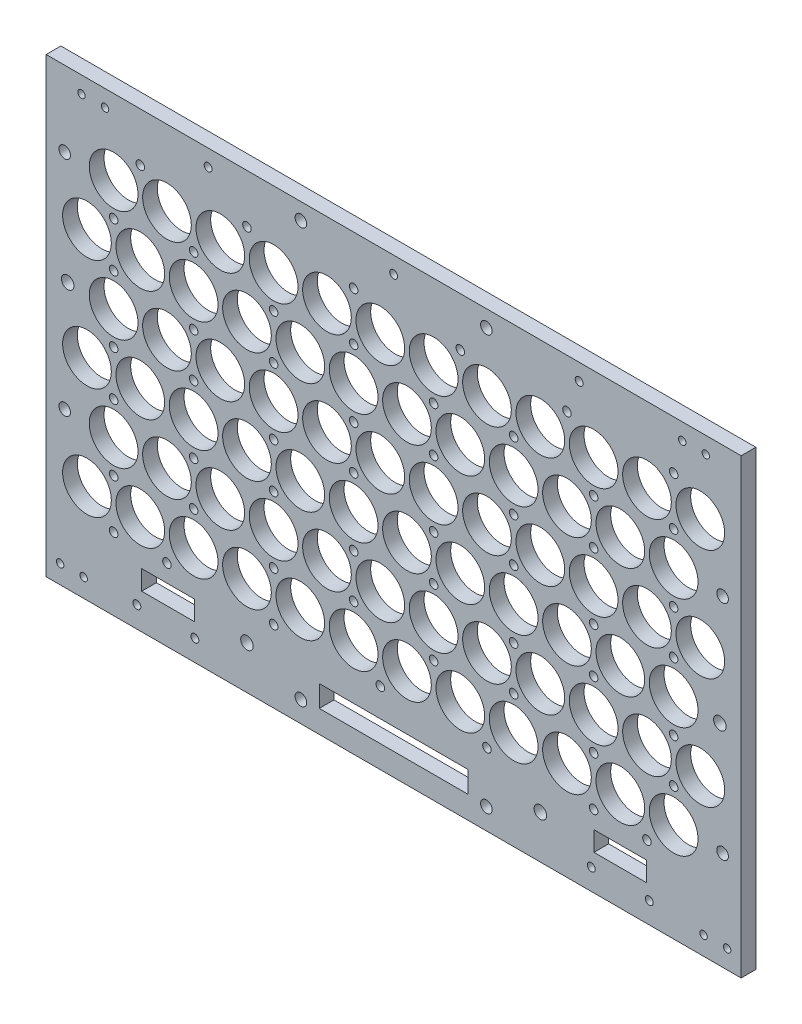
SolidWorks part; units mm, degrees
material "ABS"
ref_plane "X-Y Datum" through (0, 0, 0) normal (0, 0, 1) x (1, 0, 0)
ref_plane "X-Z Datum" through (0, 0, 0) normal (0, 1, 0) x (1, 0, 0)
ref_plane "Y-Z Datum" through (0, 0, 0) normal (1, 0, 0) x (0, 0, -1)
sketch "Sketch1" plane through (0, 0, 0) normal (0, 0, 1) x (1, 0, 0)
  line L1 (-143.025, 70.775) -> (143.025, 70.775)
  line L2 (-143.025, 70.775) -> (-143.025, -70.775)
  line L3 (-143.025, -70.775) -> (143.025, -70.775)
  line L4 (143.025, 70.775) -> (143.025, -70.775)
  line L5 (-143.025, 70.775) -> (143.025, -70.775) construction
  line L6 (-143.025, -70.775) -> (143.025, 70.775) construction
  line L13 (-149.85, -102.6) -> (149.85, -102.6)
  line L14 (-149.85, 91.65) -> (149.85, 91.65)
  line L15 (-149.85, 91.65) -> (-149.85, -102.6)
  line L16 (149.85, 91.65) -> (149.85, -102.6)
  line L17 (149.85, 70.775) -> (149.85, -70.775) construction
  line L18 (-143.025, 91.65) -> (143.025, 91.65) construction
  line L19 (-143.025, -102.6) -> (143.025, -102.6) construction
  line L20 (-149.85, 70.775) -> (-149.85, -70.775) construction
  line L21 (-132.25, -60) -> (-109.25, -60) construction
  circle A0 centre (-132.25, -60) radius 10.775
  circle A1 centre (-109.25, -60) radius 10.775 construction
  circle A2 centre (-120.75, -36) radius 10.775
  point P0 (0, 0)
  point P16 (-120.75, -60)
  dimension "D1" = 21.55
  dimension "D2" = 23
  dimension "D3" = 24
  dimension "D5" = 141.55
  dimension "D6" = 286.05
  dimension "D7" = 31.825
  dimension "D8" = 20.875
  dimension "D9" = 6.825
  dimension "D10" = 6.825
extrude "Boss-Extrude1" add sketch "Sketch1" along normal blind 6.35 contours A0 L3 L4 L1 L2 A2 | A2 | A0 | A0 L2 L3 | L1 L4 L3 L2 region at (2.4105, 0.9241, 0) region at (-140.6182, -68.3682, 0) region at (-132.25, -60, 0) region at (-146.2785, -5.475, 0) region at (-120.75, -36, 0)
sketch "Sketch3" plane through (0, 0, 6.35) normal (0, 0, 1) x (1, 0, 0)
  line L4 (143.025, 70.775) -> (-143.025, 70.775)
  line L5 (143.025, -70.775) -> (143.025, 70.775)
  line L6 (-143.025, -70.775) -> (143.025, -70.775)
  line L7 (-143.025, 70.775) -> (-143.025, -70.775)
  line L8 (143.025, 70.775) -> (-143.025, 70.775)
  line L9 (143.025, -70.775) -> (143.025, 70.775)
  line L10 (-143.025, -70.775) -> (143.025, -70.775)
  line L11 (-143.025, 70.775) -> (-143.025, -70.775)
  circle A0 centre (-132.25, -60) radius 10.4988
  circle A1 centre (-120.75, -36) radius 10.775
  circle A2 centre (-120.75, -36) radius 10.775 construction
  circle A3 centre (-132.25, -60) radius 10.775
  circle A4 centre (-132.25, -60) radius 10.775 construction
  circle A5 centre (-120.75, -36) radius 10.4988
  dimension "D4" = 20.9976
  dimension "D1" = 0
  dimension "D2" = 0
  dimension "D3" = 0
extrude "Cut-Extrude1" cut sketch "Sketch3" against normal through all contours A4 | A0 region at (-132.25, -60, 6.35)
sketch "Sketch4" plane through (0, 0, 6.35) normal (0, 0, 1) x (1, 0, 0)
  line L12 (143.025, 70.775) -> (-143.025, 70.775)
  line L13 (-143.025, 70.775) -> (-143.025, -70.775)
  line L14 (-143.025, -70.775) -> (143.025, -70.775)
  line L15 (143.025, -70.775) -> (143.025, 70.775)
  line L16 (143.025, 70.775) -> (-143.025, 70.775)
  line L17 (-143.025, 70.775) -> (-143.025, -70.775)
  line L18 (-143.025, -70.775) -> (143.025, -70.775)
  line L19 (143.025, -70.775) -> (143.025, 70.775)
  circle A1 centre (-120.75, -36) radius 10.4988
  circle A3 centre (-120.75, -36) radius 10.4988
  circle A5 centre (-132.25, -60) radius 10.4988
  circle A6 centre (-132.25, -60) radius 10.4988
  dimension "D1" = 0
  dimension "D2" = 0
  dimension "D3" = 0
extrude "Cut-Extrude2" cut sketch "Sketch4" against normal through all contours A3 region at (-120.75, -36, 6.35)
pattern_linear "LPattern1" count 12 spacing 23 along (1, 0, 0) of "Cut-Extrude1", "Cut-Extrude2"
pattern_linear "LPattern2" count 3 spacing 48 along (0, 1, 0) of "LPattern1"
sketch "Sketch5" plane through (0, 0, 6.35) normal (0, 0, 1) x (1, 0, 0)
  line L4 (105.3154, -79.3475) -> (90.1846, -79.3475)
  line L5 (90.37, -80.3) -> (90.37, -83.4115)
  line L6 (90.37, -83.4115) -> (105.13, -83.4115)
  line L7 (105.13, -83.4115) -> (105.13, -80.3)
  line L8 (105.3154, -79.3475) -> (90.1846, -79.3475)
  line L9 (90.37, -80.3) -> (90.37, -83.4115)
  line L10 (90.37, -83.4115) -> (105.13, -83.4115)
  line L11 (105.13, -83.4115) -> (105.13, -80.3)
  line L12 (-108.668, -78.95) -> (-108.668, -87.4115)
  line L13 (-108.668, -87.4115) -> (-85.908, -87.4115)
  line L14 (-85.908, -87.4115) -> (-85.908, -78.95)
  line L15 (86.37, -78.95) -> (86.37, -87.4115)
  line L16 (-89.7226, -79.3475) -> (-104.8534, -79.3475)
  line L17 (-104.668, -80.3) -> (-104.668, -83.4115)
  line L18 (-104.668, -83.4115) -> (-89.908, -83.4115)
  line L19 (-89.908, -83.4115) -> (-89.908, -80.3)
  line L20 (-89.7226, -79.3475) -> (-104.8534, -79.3475)
  line L21 (-104.668, -80.3) -> (-104.668, -83.4115)
  line L22 (-104.668, -83.4115) -> (-89.908, -83.4115)
  line L23 (-89.908, -83.4115) -> (-89.908, -80.3)
  line L24 (86.37, -87.4115) -> (109.13, -87.4115)
  line L25 (109.13, -87.4115) -> (109.13, -78.95)
  line L26 (149.85, -78.95) -> (-149.85, -78.95) construction
  line L27 (149.85, -78.95) -> (-149.85, -78.95)
  line L28 (109.13, -87.4115) -> (109.13, -80.3) construction
  line L29 (86.37, -80.3) -> (86.37, -87.4115) construction
  line L30 (-85.908, -87.4115) -> (-85.908, -80.3) construction
  line L31 (-108.668, -80.3) -> (-108.668, -87.4115) construction
  arc A2 (90.37, -80.3) -> (90.1846, -79.3475) centre (87.83, -80.3) ccw
  arc A3 (105.3154, -79.3475) -> (105.13, -80.3) centre (107.67, -80.3) ccw
  arc A4 (90.37, -80.3) -> (90.1846, -79.3475) centre (87.83, -80.3) ccw
  arc A5 (105.3154, -79.3475) -> (105.13, -80.3) centre (107.67, -80.3) ccw
  arc A8 (-104.668, -80.3) -> (-104.8534, -79.3475) centre (-107.208, -80.3) ccw
  arc A9 (-89.7226, -79.3475) -> (-89.908, -80.3) centre (-87.368, -80.3) ccw
  arc A10 (-104.668, -80.3) -> (-104.8534, -79.3475) centre (-107.208, -80.3) ccw
  arc A11 (-89.7226, -79.3475) -> (-89.908, -80.3) centre (-87.368, -80.3) ccw
  dimension "D1" = 0
  dimension "D2" = 0
  dimension "D3" = 4
extrude "Cut-Extrude3" cut sketch "Sketch5" against normal through all contours L25 L27 L15 L24 L8 A5 L11 L10 L9 A4 | A5 L8 A4 L9 L10 L11 | L14 L27 L12 L13 L20 A11 L23 L22 L21 A10 | A11 L20 A10 L21 L22 L23 region at (97.75, -81.376, 6.35) region at (-97.288, -83.9995, 6.35) region at (97.75, -83.9995, 6.35) region at (-97.288, -81.376, 6.35)
sketch "Sketch7" plane through (0, 0, 6.35) normal (0, 0, 1) x (1, 0, 0)
  point P0 (0, 85.3)
  point P1 (80, 85.3)
  point P3 (-124.45, 85.3)
  point P5 (-134.61, 85.3)
  point P7 (-133.6575, -94.6)
  point P9 (-143.8175, -94.6)
  point P11 (133.6575, -94.6)
  point P13 (143.8175, -94.6)
  point P17 (124.45, 85.3)
  point P19 (134.61, 85.3)
  point P21 (110.25, -93.5057)
  point P23 (85.25, -93.5057)
  point P28 (-80, 85.3)
hole_wizard "M3 Clearance Hole1" positions "Sketch8" profile "Sketch9" hole size "M3" standard "ANSI Metric" end condition through all
sketch "Sketch8" plane through (0, 0, 6.35) normal (0, 0, 1) x (1, 0, 0)
  point P3 (124.45, 85.3)
  point P6 (134.61, 85.3)
  point P12 (-124.45, 85.3)
  point P15 (-134.61, 85.3)
  point P18 (-143.8175, -94.6)
  point P21 (-133.6575, -94.6)
  point P24 (133.6575, -94.6)
  point P27 (143.8175, -94.6)
sketch "Sketch9" plane through (124.45, 85.3, 6.35) normal (1, 0, 0) x (0, -1, 0)
  line L0 (0, 0) -> (0, 6.35)
  line L1 (0, 6.35) -> (1.6, 6.35)
  line L2 (1.6, 6.35) -> (1.6, 0)
  line L5 (1.6, 0) -> (0, 0)
  line L11 (0, -6.35) -> (0, 107.95) construction
  dimension "Thru Hole Dia." = 3.2
  dimension "Thru Hole Depth" = 6.35
hole_wizard "M3 Clearance Hole2" positions "Sketch20" profile "Sketch13" hole size "M3" standard "ANSI Metric" end condition through all
sketch "Sketch20" plane through (0, 0, 6.35) normal (0, 0, 1) x (1, 0, 0)
  point P0 (110.25, -93.5057)
  point P3 (85.25, -93.5057)
  point P6 (-80, 85.3)
  point P9 (0, 85.3)
  point P12 (80, 85.3)
sketch "Sketch13" plane through (110.25, -93.5057, 6.35) normal (1, 0, 0) x (0, -1, 0)
  line L0 (0, 0) -> (0, 6.35)
  line L1 (0, 6.35) -> (1.7, 6.35)
  line L2 (1.7, 6.35) -> (1.7, 0)
  line L5 (1.7, 0) -> (0, 0)
  line L11 (0, -6.35) -> (0, 107.95) construction
  dimension "Thru Hole Dia." = 3.4
  dimension "Thru Hole Depth" = 6.35
sketch "Sketch14" plane through (0, 0, 6.35) normal (0, 0, 1) x (1, 0, 0)
  line L0 (131.525, -12) -> (149.85, -12) construction
  line L1 (149.85, 91.65) -> (149.85, -102.6) construction
  line L2 (-131.2488, 12) -> (-149.85, 12) construction
  line L3 (-149.85, 91.65) -> (-149.85, -102.6) construction
  line L4 (149.85, -78.95) -> (-149.85, -78.95) construction
  line L5 (149.85, -78.95) -> (-149.85, -78.95) construction
  line L6 (149.85, -83.95) -> (-149.85, -83.95) construction
  line L7 (68.55, -70.9014) -> (57.95, -70.9014) construction
  line L8 (68.55, -67.0427) -> (68.55, -74.76) construction
  line L9 (57.95, -67.0427) -> (57.95, -74.76) construction
  line L10 (63.25, -70.9014) -> (63.25, -83.95) construction
  line L18 (0, -3.4925) -> (0, 3.4925) construction
  circle A1 centre (-120.75, 12) radius 10.4988 construction
  circle A2 centre (140.6875, -12) radius 2.7
  circle A3 centre (-140.5494, 12) radius 2.7
  circle A4 centre (63.25, -83.95) radius 2.7
  circle A6 centre (-63.25, -83.95) radius 2.7
  circle A8 centre (0, -83.95) radius 2.7
  dimension "D1" = 5.4
  dimension "D3" = 5.4
  dimension "D2" = 5
extrude "Cut-Extrude4" cut sketch "Sketch14" against normal through all contours A6 | A4 | A3 | A2 region at (-140.5494, 12, 6.35) region at (63.25, -83.95, 6.35) region at (-63.25, -83.95, 6.35)
sketch "Sketch15" plane through (0, 0, 6.35) normal (0, 0, 1) x (1, 0, 0)
  line L0 (-6.35, 85.3) -> (86.35, 85.3) construction
  line L1 (-6.35, 90.65) -> (-6.35, 79.95) construction
  line L2 (86.35, 79.95) -> (86.35, 90.65) construction
  line L3 (-86.35, 85.3) -> (6.35, 85.3) construction
  line L4 (-86.35, 90.65) -> (-86.35, 79.95) construction
  line L5 (6.35, 79.95) -> (6.35, 90.65) construction
  line L6 (131.525, 36) -> (149.85, 36) construction
  line L7 (149.85, 94.825) -> (149.85, -105.775) construction
  line L8 (131.525, -60) -> (149.85, -60) construction
  line L9 (-131.2488, -36) -> (-149.85, -36) construction
  line L10 (-149.85, -105.775) -> (-149.85, 94.825) construction
  line L11 (-131.2488, 60) -> (-149.85, 60) construction
  line L12 (-40, 85.3) -> (-40, -102.6) construction
  line L13 (-149.85, -102.6) -> (149.85, -102.6) construction
  line L14 (40, 85.3) -> (40, -102.6) construction
  line L16 (85.25, -93.5057) -> (-85.25, -93.5057) construction
  circle A0 centre (-40, 85.3) radius 2.5
  circle A1 centre (40, 85.3) radius 2.5
  circle A4 centre (141.85, 36) radius 2.5
  circle A5 centre (141.85, -60) radius 2.5
  circle A6 centre (-120.75, -36) radius 10.4988 construction
  circle A7 centre (-120.75, 60) radius 10.4988 construction
  circle A8 centre (-141.85, -36) radius 2.5
  circle A9 centre (-141.85, 60) radius 2.5
  circle A10 centre (-40, -93.5057) radius 2.5
  circle A11 centre (40, -93.5057) radius 2.5
  dimension "D1" = 5
  dimension "D2" = 8
  dimension "D3" = 8
  dimension "D4" = 8
  dimension "D5" = 8
extrude "Cut-Extrude5" cut sketch "Sketch15" against normal through all
sketch "Sketch18" plane through (0, 0, 6.35) normal (0, 0, 1) x (1, 0, 0)
  circle A0 centre (-120.75, -71.41) radius 1.5875 construction
  circle A1 centre (-97.75, -71.41) radius 1.5875 construction
  circle A2 centre (-51.75, -71.41) radius 1.5875 construction
  circle A3 centre (-5.75, -71.41) radius 1.5875 construction
  circle A4 centre (40.25, -71.41) radius 1.5875 construction
  circle A5 centre (-109.25, 71.41) radius 1.5875 construction
  circle A6 centre (-63.25, 71.41) radius 1.5875 construction
  circle A7 centre (-17.25, 71.41) radius 1.5875 construction
  circle A8 centre (28.75, 71.41) radius 1.5875 construction
  circle A9 centre (74.75, 71.41) radius 1.5875 construction
  circle A10 centre (120.75, 71.41) radius 1.5875 construction
  circle A11 centre (86.25, -71.41) radius 1.5875 construction
  circle A12 centre (109.25, -71.41) radius 1.5875 construction
  circle A13 centre (-120.75, -71.41) radius 1.5875 construction
  circle A14 centre (-97.75, -71.41) radius 1.5875 construction
  circle A15 centre (-51.75, -71.41) radius 1.5875 construction
  circle A16 centre (-5.75, -71.41) radius 1.5875 construction
  circle A17 centre (40.25, -71.41) radius 1.5875 construction
  circle A18 centre (-109.25, 71.41) radius 1.5875 construction
  circle A19 centre (-63.25, 71.41) radius 1.5875 construction
  circle A20 centre (-17.25, 71.41) radius 1.5875 construction
  circle A21 centre (28.75, 71.41) radius 1.5875 construction
  circle A22 centre (74.75, 71.41) radius 1.5875 construction
  circle A23 centre (120.75, 71.41) radius 1.5875 construction
  circle A24 centre (86.25, -71.41) radius 1.5875 construction
  circle A25 centre (109.25, -71.41) radius 1.5875 construction
  circle A26 centre (109.25, -71.41) radius 1.8415
  circle A27 centre (86.25, -71.41) radius 1.8415
  circle A28 centre (120.75, 71.41) radius 1.8415
  circle A29 centre (74.75, 71.41) radius 1.8415
  circle A30 centre (28.75, 71.41) radius 1.8415
  circle A31 centre (-17.25, 71.41) radius 1.8415
  circle A32 centre (-63.25, 71.41) radius 1.8415
  circle A33 centre (-109.25, 71.41) radius 1.8415
  circle A34 centre (40.25, -71.41) radius 1.8415
  circle A35 centre (-5.75, -71.41) radius 1.8415
  circle A36 centre (-51.75, -71.41) radius 1.8415
  circle A37 centre (-97.75, -71.41) radius 1.8415
  circle A38 centre (-120.75, -71.41) radius 1.8415
  dimension "D1" = 3.683
extrude "Cut-Extrude7" cut sketch "Sketch18" against normal through all
sketch "Sketch19" plane through (0, 91.65, 0) normal (0, 1, 0) x (1, 0, 0)
  line L4 (149.85, 0) -> (-149.85, 0)
  line L5 (-149.85, 0) -> (-149.85, -6.35)
  line L6 (-149.85, -6.35) -> (149.85, -6.35)
  line L7 (149.85, -6.35) -> (149.85, 0)
  line L8 (149.85, 0) -> (-149.85, 0)
  line L9 (-149.85, 0) -> (-149.85, -6.35)
  line L10 (-149.85, -6.35) -> (149.85, -6.35)
  line L11 (149.85, -6.35) -> (149.85, 0)
  dimension "D1" = 0
extrude "Boss-Extrude2" add sketch "Sketch19" along normal blind 0.7937
sketch "Sketch22" plane through (0, 0, 6.35) normal (0, 0, 1) x (1, 0, 0)
  line L0 (132.25, -36) -> (120.75, -60) construction
  line L1 (120.75, -60) -> (109.25, -36) construction
  line L2 (109.25, -36) -> (132.25, -36) construction
  line L3 (120.75, -36) -> (120.75, -60) construction
  line L4 (127.7133, -45.468) -> (113.7867, -45.468) construction
  line L5 (109.25, -36) -> (97.75, -60) construction
  line L6 (97.75, -60) -> (86.25, -36) construction
  line L7 (86.25, -36) -> (109.25, -36) construction
  line L8 (97.75, -60) -> (97.75, -36) construction
  line L9 (113.7867, -45.468) -> (90.7867, -45.468) construction
  line L10 (86.25, -36) -> (74.75, -60) construction
  line L11 (74.75, -60) -> (63.25, -36) construction
  line L12 (63.25, -36) -> (86.25, -36) construction
  line L13 (74.75, -36) -> (74.75, -60) construction
  line L14 (90.7867, -45.468) -> (67.7867, -45.468) construction
  line L15 (74.75, -60) -> (97.75, -60) construction
  line L16 (86.25, -36) -> (86.25, -60) construction
  line L17 (79.4061, -50.2829) -> (93.0939, -50.2829) construction
  circle A0 centre (132.25, -36) radius 10.4988 construction
  circle A1 centre (109.25, -36) radius 10.4988 construction
  circle A2 centre (120.75, -45.468) radius 1.8415
  circle A3 centre (86.25, -36) radius 10.4988 construction
  circle A8 centre (86.25, -50.2829) radius 1.8415
  dimension "D1" = 3.683
extrude "Cut-Extrude8" cut sketch "Sketch22" against normal through all
pattern_linear "LPattern3" count 3 spacing 48 along (0, 1, 0) of "Cut-Extrude8"
sketch "Sketch23" plane through (0, 0, 6.35) normal (0, 0, 1) x (1, 0, 0)
  line L0 (132.25, -36) -> (120.75, -12) construction
  line L1 (120.75, -12) -> (109.25, -36) construction
  line L2 (109.25, -36) -> (132.25, -36) construction
  line L3 (120.75, -36) -> (120.75, -12) construction
  line L4 (109.25, -36) -> (97.75, -12) construction
  line L5 (97.75, -12) -> (86.25, -36) construction
  line L6 (86.25, -36) -> (109.25, -36) construction
  line L7 (97.75, -36) -> (97.75, -12) construction
  line L8 (127.7133, -26.532) -> (90.7867, -26.532) construction
  line L9 (86.25, -36) -> (63.25, -36) construction
  line L10 (63.25, -36) -> (74.75, -12) construction
  line L11 (74.75, -12) -> (86.25, -36) construction
  line L12 (74.75, -36) -> (74.75, -12) construction
  line L13 (90.7867, -26.532) -> (67.7867, -26.532) construction
  line L14 (74.75, -12) -> (97.75, -12)
  line L15 (86.25, -12) -> (86.25, -36) construction
  line L16 (79.4061, -21.7171) -> (93.0939, -21.7171) construction
  circle A0 centre (132.25, -36) radius 10.4988 construction
  circle A1 centre (86.25, -36) radius 10.4988 construction
  circle A2 centre (120.75, -26.532) radius 1.8415
  circle A7 centre (86.25, -21.7171) radius 1.8415
  dimension "D1" = 3.683
extrude "Cut-Extrude9" cut sketch "Sketch23" against normal through all contours A7 | A2 region at (120.75, -26.532, 6.35) region at (86.25, -21.7171, 6.35)
pattern_linear "LPattern4" count 2 spacing 48 along (0, 1, 0) of "Cut-Extrude9"
pattern_linear "LPattern5" count 4 spacing 69 along (-1, 0, 0) of "Cut-Extrude8", "LPattern3", "Cut-Extrude9", "LPattern4"
sketch "Sketch25" plane through (0, 0, 6.35) normal (0, 0, 1) x (1, 0, 0)
  line L0 (-85.712, -93.486) -> (-110.712, -93.486)
  line L1 (-149.85, -102.6) -> (149.85, -102.6) construction
  line L3 (-149.85, 92.4437) -> (-149.85, -102.6) construction
  circle A0 centre (-110.712, -93.486) radius 1.5
  circle A1 centre (-85.712, -93.486) radius 1.5
  point P7 (-98.212, -93.486)
  dimension "D1" = 3
  dimension "D2" = 25
  dimension "D3" = 9.114
  dimension "D4" = 39.138
hole_wizard "M3 Clearance Hole3" positions "Sketch30" profile "Sketch29" hole size "M3" standard "ANSI Metric" end condition through all
sketch "Sketch30" plane through (0, 0, 6.35) normal (0, 0, 1) x (1, 0, 0)
  point P0 (-85.712, -93.486)
  point P3 (-110.712, -93.486)
sketch "Sketch29" plane through (-85.712, -93.486, 6.35) normal (1, 0, 0) x (0, -1, 0)
  line L0 (0, 0) -> (0, 6.35)
  line L1 (0, 6.35) -> (1.7, 6.35)
  line L2 (1.7, 6.35) -> (1.7, 0)
  line L5 (1.7, 0) -> (0, 0)
  line L11 (0, -6.35) -> (0, 107.95) construction
  dimension "Thru Hole Dia." = 3.4
  dimension "Thru Hole Depth" = 6.35
sketch "Sketch31" plane through (0, 0, 6.35) normal (0, 0, 1) x (1, 0, 0)
  line L0 (0, -102.6) -> (0, 92.4437) construction
  line L1 (-149.85, -102.6) -> (149.85, -102.6) construction
  line L2 (149.85, 92.4437) -> (-149.85, 92.4437) construction
  line L3 (-32.0675, -92.8738) -> (32.0675, -92.8738)
  line L4 (-30.48, -91.2863) -> (30.48, -91.2863) construction
  line L5 (-30.48, -91.2863) -> (-30.48, -85.1863) construction
  line L6 (-30.48, -85.1863) -> (30.48, -85.1863) construction
  line L7 (30.48, -91.2863) -> (30.48, -85.1863) construction
  line L8 (-30.48, -91.2863) -> (30.48, -85.1863) construction
  line L9 (-30.48, -85.1863) -> (30.48, -91.2863) construction
  line L10 (32.0675, -92.8738) -> (32.0675, -83.5988)
  line L11 (-32.0675, -83.5988) -> (32.0675, -83.5988)
  line L12 (-32.0675, -92.8738) -> (-32.0675, -83.5988)
  point P6 (0, -88.2363)
  dimension "D1" = 11.3137
  dimension "D2" = 6.1
  dimension "D3" = 60.96
  dimension "D4" = 1.5875
extrude "Cut-Extrude10" cut sketch "Sketch31" against normal through all
